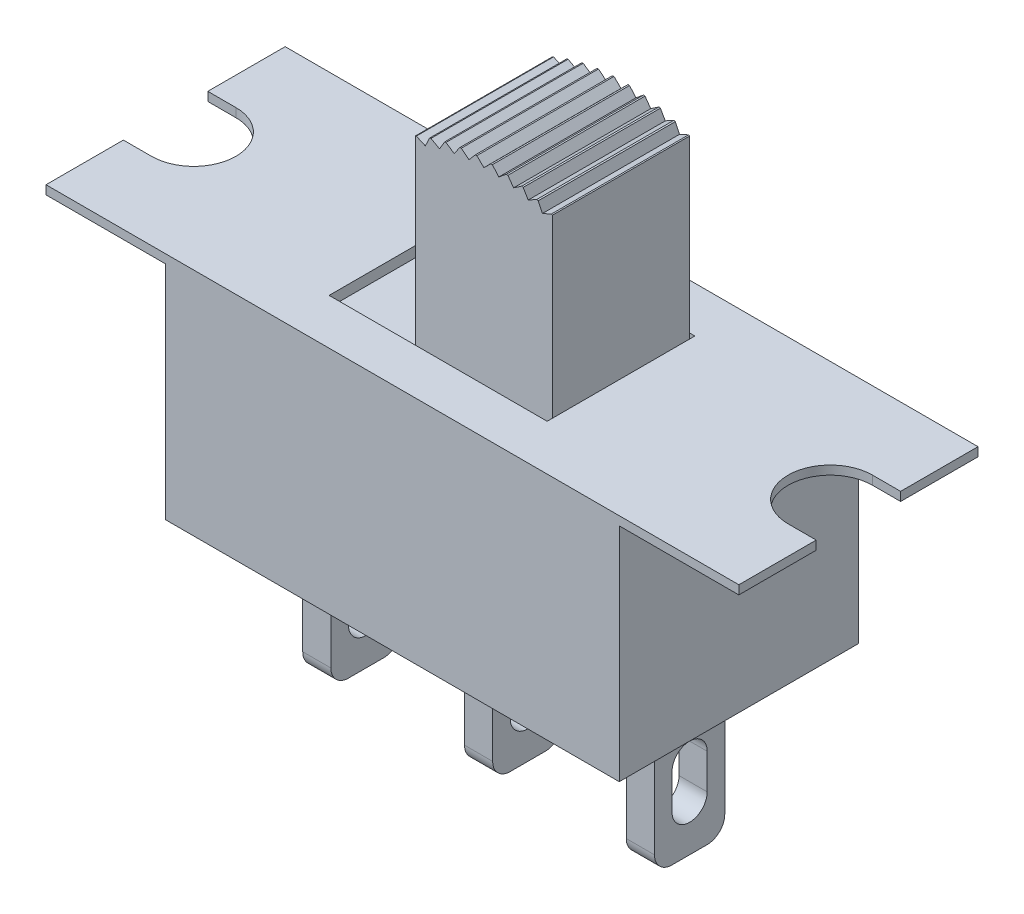
SolidWorks part; units mm, degrees
ref_plane "Plan de face" through (0, 0, 0) normal (0, 0, 1) x (1, 0, 0)
ref_plane "Plan de dessus" through (0, 0, 0) normal (0, 1, 0) x (1, 0, 0)
ref_plane "Plan de droite" through (0, 0, 0) normal (1, 0, 0) x (0, 0, -1)
sketch "Esquisse1" plane through (0, 0, 0) normal (0, 0, 1) x (1, 0, 0)
  line L1 (-6.45, 3.275) -> (6.45, 3.275)
  line L2 (-6.45, 3.025) -> (-6.45, -3.275)
  line L3 (-6.45, -3.275) -> (6.45, -3.275)
  line L4 (6.45, 3.025) -> (6.45, -3.275)
  line L5 (-6.45, 3.275) -> (6.45, -3.275) construction
  line L6 (-6.45, -3.275) -> (6.45, 3.275) construction
  line L7 (-6.45, 3.275) -> (-9.85, 3.275)
  line L9 (-6.45, 3.025) -> (-9.85, 3.025)
  line L10 (-9.85, 3.275) -> (-9.85, 3.025)
  line L11 (6.45, 3.275) -> (9.85, 3.275)
  line L13 (6.45, 3.025) -> (9.85, 3.025)
  line L14 (9.85, 3.275) -> (9.85, 3.025)
  point P0 (0, 0)
  dimension "D1" = 12.9
  dimension "D2" = 3.4
  dimension "D3" = 3.4
  dimension "D4" = 0.25
  dimension "D5" = 0.25
  dimension "D6" = 6.3
  dimension "D7" = 12.9
  dimension "D8" = 3.4
extrude "Boss.-Extru.1" add sketch "Esquisse1" along normal blind 3.4 and the other way blind 3.4
sketch "Esquisse3" plane through (0, 3.275, 0) normal (0, 1, 0) x (1, 0, 0)
  line L0 (0, 3.4) -> (0, -3.4) construction
  line L1 (9.85, 3.4) -> (-9.85, 3.4) construction
  line L2 (9.85, -3.4) -> (-9.85, -3.4) construction
  line L3 (-9.85, 0) -> (9.85, 0) construction
  line L4 (-9.85, 3.4) -> (-9.85, -3.4) construction
  line L5 (9.85, 3.4) -> (9.85, -3.4) construction
  line L6 (-9.85, 0) -> (-9.05, 0) construction
  line L7 (-9.85, 1.2) -> (-9.05, 1.2)
  line L8 (-9.85, -1.2) -> (-9.05, -1.2)
  line L9 (-9.85, 1.2) -> (-9.85, -1.2)
  line L10 (-9.85, 1.2) -> (-9.05, 1.2)
  line L11 (-9.85, -1.2) -> (-9.05, -1.2)
  line L12 (9.85, 0) -> (9.05, 0) construction
  line L13 (9.85, -1.2) -> (9.05, -1.2)
  line L14 (9.85, 1.2) -> (9.05, 1.2)
  line L15 (9.85, 1.2) -> (9.85, -1.2)
  line L16 (9.85, -1.2) -> (9.05, -1.2)
  line L17 (9.85, 1.2) -> (9.05, 1.2)
  arc A1 (-9.05, -1.2) -> (-9.05, 1.2) centre (-9.05, 0) ccw
  arc A2 (9.05, -1.2) -> (9.05, 1.2) centre (9.05, 0) cw
  point P12 (-9.05, -1.1937)
  point P18 (-9.85, -1.2)
  line M7 (-9.85, 3.4) -> (-9.85, -3.4)
  line M9 (9.85, -3.4) -> (9.85, 3.4)
  dimension "D1" = 1.2
  dimension "D2" = 0.8
extrude "Enlèv. mat.-Extru.1" cut sketch "Esquisse3" against normal blind 6.8 contours L8 A1 L7 M7 | A2 L13 L14 M9 region at (-8.9582, 3.275, 0) region at (8.9582, 3.275, 0)
sketch "Esquisse4" plane through (0, 3.275, 0) normal (0, 1, 0) x (1, 0, 0)
  line L1 (-3.1, 2.1) -> (3.1, 2.1)
  line L2 (-3.1, 2.1) -> (-3.1, -2.1)
  line L3 (-3.1, -2.1) -> (3.1, -2.1)
  line L4 (3.1, 2.1) -> (3.1, -2.1)
  line L5 (-3.1, 2.1) -> (3.1, -2.1) construction
  line L6 (-3.1, -2.1) -> (3.1, 2.1) construction
  point P0 (0, 0)
  point P5 (0, 0)
  dimension "D1" = 4.2
  dimension "D2" = 6.2
extrude "Enlèv. mat.-Extru.2" cut sketch "Esquisse4" against normal blind 0.3
sketch "Esquisse6" plane through (0, 0, 0) normal (0, 0, 1) x (1, 0, 0)
  line L0 (3.1, 2.975) -> (-3.1, 2.975) construction
  line L1 (-0.8, 2.975) -> (3.1, 2.975)
  line L2 (-0.8, 2.975) -> (-0.8, 8.275)
  line L4 (3.1, 2.975) -> (3.1, 8.275)
  line L5 (3.1, 2.975) -> (3.1, 3.275) construction
  line L6 (1.15, 8.4709) -> (1.15, 3.6709) construction
  line L7 (0.95, 8.6669) -> (1.15, 8.4709)
  line L8 (1.15, 8.4709) -> (1.35, 8.6669)
  line L9 (1.3923, 8.665) -> (1.5742, 8.4521)
  line L10 (1.5742, 8.4521) -> (1.7908, 8.6297)
  line L11 (1.8328, 8.6241) -> (1.9951, 8.3959)
  line L12 (1.9951, 8.3959) -> (2.2265, 8.5537)
  line L13 (2.2679, 8.5444) -> (2.4094, 8.3028)
  line L14 (2.4094, 8.3028) -> (2.6538, 8.4394)
  line L15 (2.6942, 8.4265) -> (2.8139, 8.1733)
  line L16 (2.8139, 8.1733) -> (3.0694, 8.2878)
  line L141 (-0.7694, 8.2878) -> (-0.5139, 8.1733)
  line L142 (-0.5139, 8.1733) -> (-0.3942, 8.4265)
  line L143 (-0.3538, 8.4394) -> (-0.1094, 8.3028)
  line L144 (-0.1094, 8.3028) -> (0.0321, 8.5444)
  line L145 (0.0735, 8.5537) -> (0.3049, 8.3959)
  line L146 (0.3049, 8.3959) -> (0.4672, 8.6241)
  line L147 (0.5092, 8.6297) -> (0.7258, 8.4521)
  line L148 (0.7258, 8.4521) -> (0.9077, 8.665)
  line L149 (-3.5926, 4.4113) -> (-3.7554, 4.6392) [skipped]
  line L150 (-3.747, 4.6807) -> (-3.5086, 4.8276) [skipped]
  line L151 (-3.5086, 4.8276) -> (-3.6506, 5.0689) [skipped]
  line L152 (-3.6386, 5.1095) -> (-3.3881, 5.2348) [skipped]
  line L153 (-3.3881, 5.2348) -> (-3.5082, 5.4877) [skipped]
  line L154 (-3.4927, 5.5271) -> (-3.2321, 5.6297) [skipped]
  line L155 (-3.2321, 5.6297) -> (-3.3295, 5.8923) [skipped]
  line L156 (-3.3105, 5.9302) -> (-3.0419, 6.0094) [skipped]
  line L157 (-3.0419, 6.0094) -> (-3.1156, 6.2795) [skipped]
  line L158 (-3.0933, 6.3156) -> (-2.8188, 6.3707) [skipped]
  line L159 (-2.8188, 6.3707) -> (-2.8684, 6.6463) [skipped]
  line L160 (-2.843, 6.6802) -> (-2.5647, 6.7109) [skipped]
  line L161 (-2.5647, 6.7109) -> (-2.5897, 6.9898) [skipped]
  line L162 (-2.5614, 7.0214) -> (-2.2814, 7.0273) [skipped]
  line L163 (-2.2814, 7.0273) -> (-2.2817, 7.3073) [skipped]
  line L164 (-1.5523, 7.8778) -> (-1.2806, 7.81) [skipped]
  line L165 (-1.6369, 7.579) -> (-1.5879, 7.8547) [skipped]
  line L166 (-1.9135, 7.6225) -> (-1.6369, 7.579) [skipped]
  line L167 (-1.9714, 7.3174) -> (-1.9469, 7.5964) [skipped]
  line L168 (-2.2508, 7.3363) -> (-1.9714, 7.3174) [skipped]
  line L169 (-3.8171, 4.2439) -> (-3.5926, 4.4113) [skipped]
  line L170 (-3.6394, 3.9893) -> (-3.8217, 4.2018) [skipped]
  line L171 (-3.8483, 3.8027) -> (-3.6394, 3.9893) [skipped]
  line L172 (-3.6488, 3.5647) -> (-3.8492, 3.7604) [skipped]
  line L173 (-3.8404, 3.3605) -> (-3.6488, 3.5647) [skipped]
  line L174 (-3.6207, 3.141) -> (-3.8375, 3.3182) [skipped]
  line L175 (-3.7934, 2.9206) -> (-3.6207, 3.141) [skipped]
  line L176 (-3.5552, 2.7215) -> (-3.7868, 2.8788) [skipped]
  line L177 (-3.4233, 1.6499) -> (-3.3145, 1.9079) [skipped]
  line L178 (-3.3145, 1.9079) -> (-3.5702, 2.0219) [skipped]
  line L179 (-3.5841, 2.062) -> (-3.4528, 2.3093) [skipped]
  line L180 (-3.4528, 2.3093) -> (-3.6975, 2.4455) [skipped]
  line L181 (-3.7077, 2.4867) -> (-3.5552, 2.7215) [skipped]
  line L182 (-2.9343, 1.1494) -> (-3.2062, 1.2166) [skipped]
  line L183 (-3.2268, 1.2536) -> (-3.1412, 1.5202) [skipped]
  line L184 (-2.996, 0.8762) -> (-2.9343, 1.1494) [skipped]
  line L185 (-2.6955, 0.7983) -> (-2.9722, 0.8412) [skipped]
  line L186 (-2.4392, 0.1899) -> (-2.4266, 0.4696) [skipped]
  line L187 (-2.1296, 0.1661) -> (-2.4096, 0.1596) [skipped]
  line L188 (-2.1175, -0.1137) -> (-2.1296, 0.1661) [skipped]
  line L189 (-1.807, -0.1101) -> (-2.0853, -0.1413) [skipped]
  line L190 (-1.7702, -0.3877) -> (-1.807, -0.1101) [skipped]
  line L191 (-1.4613, -0.3566) -> (-1.7357, -0.4123) [skipped]
  line L192 (-1.4001, -0.6299) -> (-1.4613, -0.3566) [skipped]
  line L193 (-1.0951, -0.5716) -> (-1.3636, -0.6513) [skipped]
  line L194 (-1.01, -0.8384) -> (-1.0951, -0.5716) [skipped]
  line L195 (-0.7114, -0.7535) -> (-0.9717, -0.8566) [skipped]
  line L196 (-0.603, -1.0117) -> (-0.7114, -0.7535) [skipped]
  line L197 (0.5147, -1.0868) -> (0.2905, -1.2546) [skipped]
  line L198 (0.687, -1.3076) -> (0.5147, -1.0868) [skipped]
  line L199 (0.9377, -1.1244) -> (0.7292, -1.3113) [skipped]
  line L200 (1.1288, -1.329) -> (0.9377, -1.1244) [skipped]
  line L201 (1.3623, -1.1244) -> (1.1712, -1.329) [skipped]
  line L202 (1.5708, -1.3113) -> (1.3623, -1.1244) [skipped]
  line L203 (1.7853, -1.0868) -> (1.613, -1.3076) [skipped]
  line L204 (2.0095, -1.2546) -> (1.7853, -1.0868) [skipped]
  line L205 (2.2033, -1.0121) -> (2.0512, -1.2472) [skipped]
  line L206 (2.4414, -1.1594) -> (2.2033, -1.0121) [skipped]
  line L207 (2.6131, -0.9007) -> (2.4823, -1.1483) [skipped]
  line L208 (2.8633, -1.0264) -> (2.6131, -0.9007) [skipped]
  line L209 (3.0114, -0.7535) -> (2.903, -1.0117) [skipped]
  line L210 (3.2717, -0.8566) -> (3.0114, -0.7535) [skipped]
  line L211 (3.3951, -0.5716) -> (3.31, -0.8384) [skipped]
  line L212 (3.6636, -0.6513) -> (3.3951, -0.5716) [skipped]
  line L213 (3.7613, -0.3566) -> (3.7001, -0.6299) [skipped]
  line L214 (4.0357, -0.4123) -> (3.7613, -0.3566) [skipped]
  line L215 (4.107, -0.1101) -> (4.0702, -0.3877) [skipped]
  line L216 (4.3853, -0.1413) -> (4.107, -0.1101) [skipped]
  line L217 (4.4296, 0.1661) -> (4.4175, -0.1137) [skipped]
  line L218 (-0.3131, -0.9007) -> (-0.5633, -1.0264) [skipped]
  line L219 (-0.1823, -1.1483) -> (-0.3131, -0.9007) [skipped]
  line L220 (0.0967, -1.0121) -> (-0.1414, -1.1594) [skipped]
  line L221 (0.2488, -1.2472) -> (0.0967, -1.0121) [skipped]
  line L222 (-3.1412, 1.5202) -> (-3.406, 1.6112) [skipped]
  line L223 (-2.7328, 0.5207) -> (-2.6955, 0.7983) [skipped]
  line L224 (-2.4266, 0.4696) -> (-2.706, 0.4879) [skipped]
  line L225 (4.7096, 0.1596) -> (4.4296, 0.1661) [skipped]
  line L226 (4.7266, 0.4696) -> (4.7392, 0.1899) [skipped]
  line L227 (5.006, 0.4879) -> (4.7266, 0.4696) [skipped]
  line L228 (4.9955, 0.7983) -> (5.0328, 0.5207) [skipped]
  line L229 (5.2722, 0.8412) -> (4.9955, 0.7983) [skipped]
  line L230 (5.2343, 1.1494) -> (5.296, 0.8762) [skipped]
  line L231 (5.5062, 1.2166) -> (5.2343, 1.1494) [skipped]
  line L232 (5.4412, 1.5202) -> (5.5268, 1.2536) [skipped]
  line L233 (5.706, 1.6112) -> (5.4412, 1.5202) [skipped]
  line L234 (5.6145, 1.9079) -> (5.7233, 1.6499) [skipped]
  line L235 (5.8702, 2.0219) -> (5.6145, 1.9079) [skipped]
  line L236 (5.7528, 2.3093) -> (5.8841, 2.062) [skipped]
  line L237 (5.9975, 2.4455) -> (5.7528, 2.3093) [skipped]
  line L238 (5.8552, 2.7215) -> (6.0077, 2.4867) [skipped]
  line L239 (6.0868, 2.8788) -> (5.8552, 2.7215) [skipped]
  line L240 (5.9207, 3.141) -> (6.0934, 2.9206) [skipped]
  line L241 (6.1375, 3.3182) -> (5.9207, 3.141) [skipped]
  line L242 (5.9488, 3.5647) -> (6.1404, 3.3605) [skipped]
  line L243 (6.1492, 3.7604) -> (5.9488, 3.5647) [skipped]
  line L244 (5.9394, 3.9893) -> (6.1483, 3.8027) [skipped]
  line L245 (6.1217, 4.2018) -> (5.9394, 3.9893) [skipped]
  line L246 (5.8082, 5.4877) -> (5.6881, 5.2348) [skipped]
  line L247 (5.5321, 5.6297) -> (5.7927, 5.5271) [skipped]
  line L248 (5.6295, 5.8923) -> (5.5321, 5.6297) [skipped]
  line L249 (5.6881, 5.2348) -> (5.9386, 5.1095) [skipped]
  line L250 (5.9506, 5.0689) -> (5.8086, 4.8276) [skipped]
  line L251 (5.8086, 4.8276) -> (6.047, 4.6807) [skipped]
  line L252 (6.0554, 4.6392) -> (5.8926, 4.4113) [skipped]
  line L253 (5.8926, 4.4113) -> (6.1171, 4.2439) [skipped]
  line L254 (5.3419, 6.0094) -> (5.6105, 5.9302) [skipped]
  line L255 (5.4156, 6.2795) -> (5.3419, 6.0094) [skipped]
  line L256 (5.1188, 6.3707) -> (5.3933, 6.3156) [skipped]
  line L257 (5.1684, 6.6463) -> (5.1188, 6.3707) [skipped]
  line L258 (4.8647, 6.7109) -> (5.143, 6.6802) [skipped]
  line L259 (4.8897, 6.9898) -> (4.8647, 6.7109) [skipped]
  line L260 (4.5814, 7.0273) -> (4.8614, 7.0214) [skipped]
  line L261 (4.5817, 7.3073) -> (4.5814, 7.0273) [skipped]
  line L262 (4.2714, 7.3174) -> (4.5508, 7.3363) [skipped]
  line L263 (4.2469, 7.5964) -> (4.2714, 7.3174) [skipped]
  line L264 (3.9369, 7.579) -> (4.2135, 7.6225) [skipped]
  line L265 (3.8879, 7.8547) -> (3.9369, 7.579) [skipped]
  line L266 (3.5806, 7.81) -> (3.8523, 7.8778) [skipped]
  line L267 (3.5074, 8.0803) -> (3.5806, 7.81) [skipped]
  line L268 (3.2053, 8.0087) -> (3.4699, 8.1001) [skipped]
  line L269 (3.1084, 8.2714) -> (3.2053, 8.0087) [skipped]
  line L270 (-0.9053, 8.0087) -> (-0.8084, 8.2714) [skipped]
  line L271 (-1.1699, 8.1001) -> (-0.9053, 8.0087) [skipped]
  line L272 (-1.2806, 7.81) -> (-1.2074, 8.0803) [skipped]
  arc A0 (-0.8, 8.275) -> (-0.7694, 8.2878) centre (1.15, 3.6709) cw
  arc A1 (1.35, 8.6669) -> (1.3923, 8.665) centre (1.15, 3.6709) cw
  arc A2 (3.0694, 8.2878) -> (3.1, 8.275) centre (1.15, 3.6709) cw
  arc A3 (2.6538, 8.4394) -> (2.6942, 8.4265) centre (1.15, 3.6709) cw
  arc A4 (2.2265, 8.5537) -> (2.2679, 8.5444) centre (1.15, 3.6709) cw
  arc A5 (1.7908, 8.6297) -> (1.8328, 8.6241) centre (1.15, 3.6709) cw
  arc A6 (0.9077, 8.665) -> (0.95, 8.6669) centre (1.15, 3.6709) cw
  arc A7 (0.4672, 8.6241) -> (0.5092, 8.6297) centre (1.15, 3.6709) cw
  arc A8 (0.0321, 8.5444) -> (0.0735, 8.5537) centre (1.15, 3.6709) cw
  arc A9 (-0.3942, 8.4265) -> (-0.3538, 8.4394) centre (1.15, 3.6709) cw
  point P225 (1.15, 3.6709)
  dimension "D4" = 5
  dimension "D1" = 5.3
  dimension "D2" = 3.9
  dimension "D3" = 5.3
  dimension "D5" = 4.8
  dimension "D6" = 0.4
  dimension "D7" = 0.2
  dimension "D8" = 0.2
  dimension "D9" = 71
extrude "Boss.-Extru.2" add sketch "Esquisse6" along normal blind 1.95 and the other way blind 1.95
sketch "Esquisse7" plane through (0, -3.275, 0) normal (0, -1, 0) x (1, 0, 0)
  line L0 (-6.45, -3.4) -> (-6.45, 3.4) construction
  line L1 (-4.95, 1) -> (-4.15, 1)
  line L2 (-4.95, 1) -> (-4.95, -1)
  line L3 (-4.95, -1) -> (-4.15, -1)
  line L4 (-4.15, 1) -> (-4.15, -1)
  line L13 (-6.45, 0) -> (6.45, 0) construction
  line L14 (-6.45, -3.4) -> (-6.45, 3.4) construction
  line L15 (6.45, -3.4) -> (6.45, 3.4) construction
  line L16 (-0.35, 1) -> (-0.35, -1)
  line L17 (-0.35, 1) -> (0.45, 1)
  line L18 (0.45, 1) -> (0.45, -1)
  line L19 (-0.35, -1) -> (0.45, -1)
  line L20 (4.25, 1) -> (4.25, -1)
  line L21 (4.25, 1) -> (5.05, 1)
  line L22 (5.05, 1) -> (5.05, -1)
  line L23 (4.25, -1) -> (5.05, -1)
  point P12 (-4.95, 0)
  dimension "D1" = 0.8
  dimension "D2" = 2
  dimension "D3" = 1.5
  dimension "D4" = 3
extrude "Boss.-Extru.3" add sketch "Esquisse7" along normal blind 4.2
fillet "Congé1" radius 0.5 6 edges at (-4.55, -7.475, -1) (0.05, -7.475, -1) (4.65, -7.475, -1) (0.05, -7.475, 1) (4.65, -7.475, 1) (-4.55, -7.475, 1)
sketch "Esquisse8" plane through (5.05, 0, 0) normal (1, 0, 0) x (0, 0, -1)
  line L0 (0, -5.175) -> (0, -6.175) construction
  line L1 (0.5, -5.175) -> (0.5, -6.175)
  line L2 (-0.5, -5.175) -> (-0.5, -6.175)
  line L3 (0.5, -7.475) -> (-0.5, -7.475) construction
  arc A0 (0.5, -5.175) -> (-0.5, -5.175) centre (0, -5.175) ccw
  arc A1 (-0.5, -6.175) -> (0.5, -6.175) centre (0, -6.175) ccw
  point P3 (0, -5.675)
  dimension "D1" = 1
  dimension "D2" = 1
  dimension "D3" = 1.3
extrude "Enlèv. mat.-Extru.3" cut sketch "Esquisse8" against normal blind 10.2
